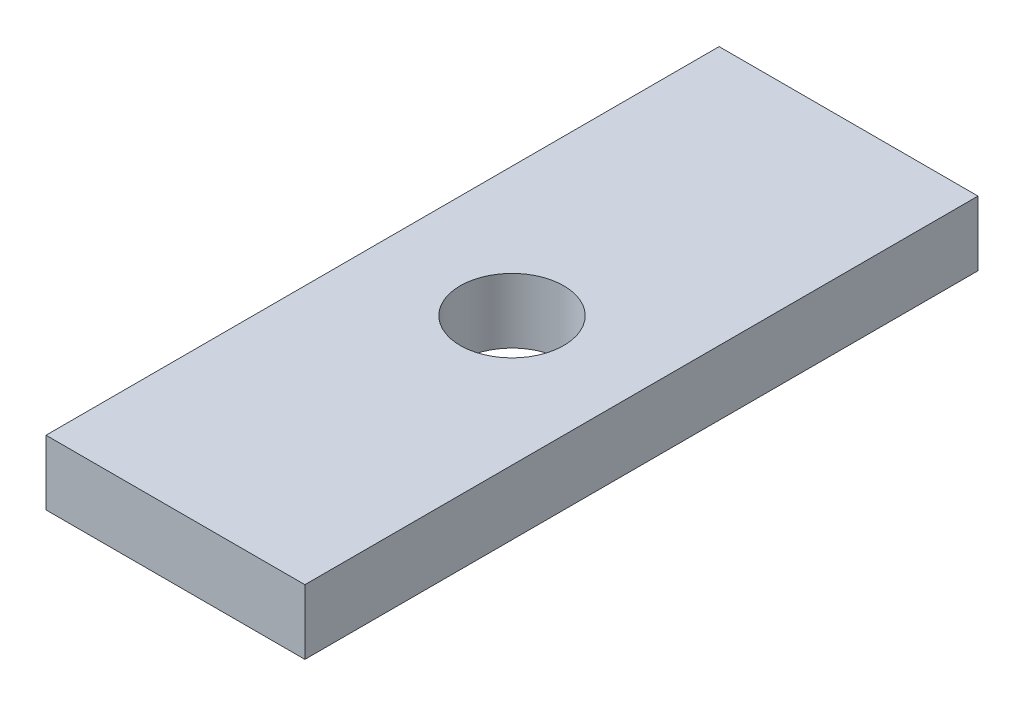
SolidWorks part; units mm, degrees
material "AISI 1045 Steel, cold drawn"
ref_plane "Front Plane" through (0, 0, 0) normal (0, 0, 1) x (1, 0, 0)
ref_plane "Top Plane" through (0, 0, 0) normal (0, 1, 0) x (1, 0, 0)
ref_plane "Right Plane" through (0, 0, 0) normal (1, 0, 0) x (0, 0, -1)
sketch "Sketch1" plane through (0, 0, 0) normal (0, 0, 1) x (1, 0, 0)
  line L1 (-10, 2.5) -> (10, 2.5)
  line L2 (-10, 2.5) -> (-10, -2.5)
  line L3 (-10, -2.5) -> (10, -2.5)
  line L4 (10, 2.5) -> (10, -2.5)
  point P4 (10, 0)
  point P6 (0, 2.5)
  dimension "D1" = 20
  dimension "D2" = 5
extrude "Boss-Extrude1" add sketch "Sketch1" along normal mid plane 212
sketch "Sketch2" plane through (0, 2.5, 0) normal (0, 1, 0) x (1, 0, 0)
  line L0 (0, 0) -> (35.2363, 0) construction
  circle A0 centre (0, 87.5) radius 4
  circle A1 centre (0, 0) radius 4
  circle A2 centre (0, -87.5) radius 4
  dimension "D1" = 8
  dimension "D2" = 175
extrude "Holes for 20mm strip ONLY" cut sketch "Sketch2" against normal through all
sketch "Sketch3" [suppressed] plane through (0, 2.5, 0) normal (0, 1, 0) x (1, 0, 0)
  line L0 (0, 0) -> (65.8821, 0) construction
  line L1 (15, -175) -> (-15, -175) construction
  circle A0 centre (0, -50) radius 2.5
  circle A1 centre (0, -150) radius 2.5
  circle A2 centre (0, 150) radius 2.5
  circle A3 centre (0, 50) radius 2.5
  point P7 (0, -175)
  dimension "D2" = 5
  dimension "D1" = 100
  dimension "D3" = 300
extrude "Cut-Extrude1" [suppressed] cut sketch "Sketch3" against normal through all
sketch "Sketch4" plane through (0, 2.5, 0) normal (0, 1, 0) x (1, 0, 0)
  line L0 (-10, -106) -> (-10, 106) construction
  line L1 (10, -26) -> (-10, -26)
  line L2 (10, -26) -> (10, 26)
  line L3 (10, 26) -> (-10, 26)
  line L4 (-10, -26) -> (-10, 26)
  line L5 (10, -26) -> (-10, 26) construction
  line L6 (10, 26) -> (-10, -26) construction
  point P0 (0, 0)
  dimension "D1" = 52
extrude "Cut-Extrude2" cut sketch "Sketch4" against normal through all flip side to cut
